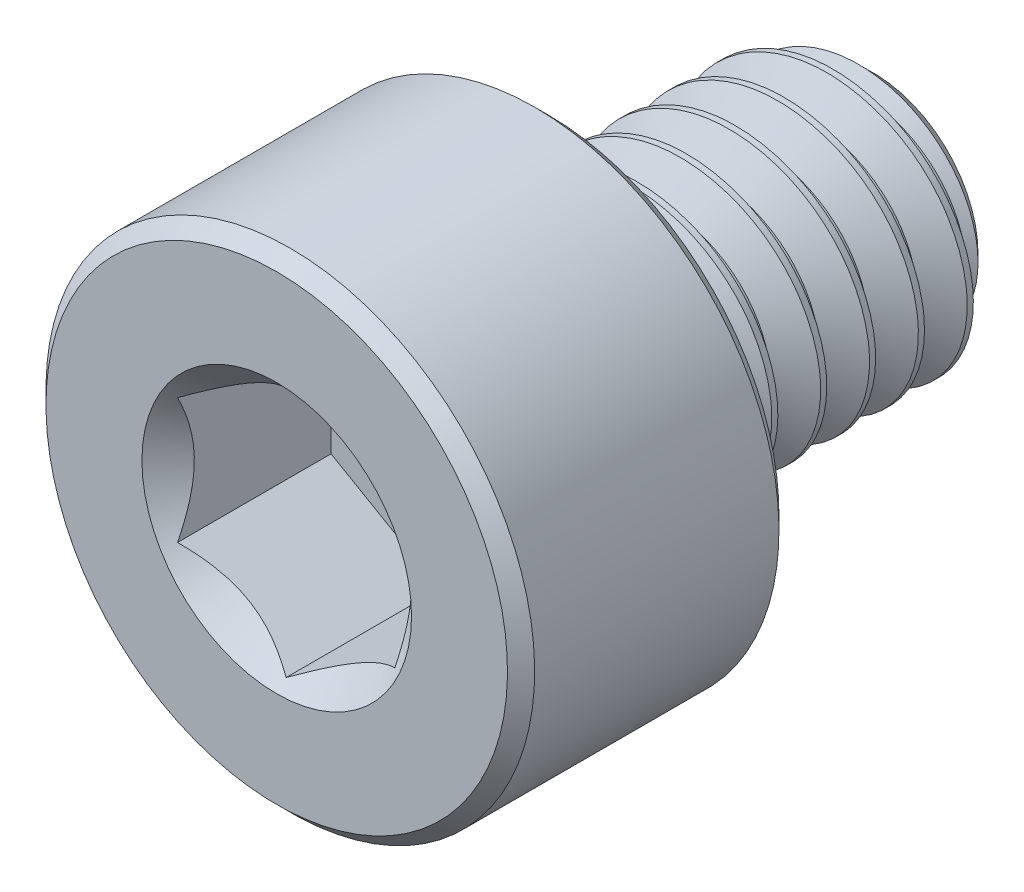
SolidWorks part; units mm, degrees
ref_plane "Front Plane" through (0, 0, 0) normal (0, 0, 1) x (1, 0, 0)
ref_plane "Top Plane" through (0, 0, 0) normal (0, 1, 0) x (1, 0, 0)
ref_plane "Right Plane" through (0, 0, 0) normal (1, 0, 0) x (0, 0, -1)
sketch "Sketch1" plane through (0, 0, 0) normal (1, 0, 0) x (0, 0, -1)
  line L0 (-2.75, 0) -> (2.75, 0) construction
  line L1 (2.75, 0) -> (2.75, 0.9577) construction
  line L2 (2.75, 0.9577) -> (2.4577, 1.25) construction
  line L3 (2.4577, 1.25) -> (2.4125, 1.25) construction
  line L4 (2.4125, 1.25) -> (-0.25, 1.25) construction
  line L5 (-0.25, 1.25) -> (-0.25, 2.25) construction
  line L6 (-0.25, 2.25) -> (-2.75, 2.25) construction
  line L7 (-2.75, 2.25) -> (-2.75, 0) construction
  line L8 (2.75, 0.9577) -> (2.75, 1.25) construction
  line L9 (2.7219, 1.2987) -> (2.9469, 0.909) construction
  line L10 (2.9469, 0.909) -> (3.1719, 1.2987) construction
  line L11 (3.1719, 1.2987) -> (2.7219, 1.2987) construction
  line L12 (2.9469, 1.2987) -> (2.9469, 1.25) construction
  line L13 (2.9469, 0.909) -> (2.9469, 0.9577) construction
  line L14 (2.9187, 0.9577) -> (2.975, 0.9577) construction
  line L15 (2.75, 1.25) -> (3.1437, 1.25) construction
  line L16 (2.7359, 1.2744) -> (3.1578, 1.2744) construction
  line L17 (2.75, 0) -> (2.75, -1.25) construction
  line L18 (-0.375, 2.25) -> (-0.25, 2.125) construction
  line L19 (-2.625, 2.25) -> (-2.75, 2.125) construction
  line L20 (-0.25, 1.25) -> (-0.25, 0) construction
  line L21 (-0.25, 0.625) -> (0.75, 0.625) construction
  line L22 (0.75, 0.625) -> (1.75, 0.625) construction
  line L23 (1.75, 0.625) -> (2.75, 0.625) construction
  line L24 (0.75, 0.625) -> (0.75, 1.25) construction
  line L25 (0.75, 1.25) -> (0.75, 2.25) construction
  line L26 (1.75, 0.625) -> (1.75, 2.25) construction
  point P0 (-2.75, 1)
  point P3 (1.625, 1.25)
  point P4 (0, 0)
  point P18 (1.75, 1.25)
  point P22 (2.9469, 0.9577)
  point P24 (2.4125, 1.25)
  point P25 (2.9469, 1.25)
  point P28 (2.9469, 1.2744)
  point P29 (1.625, -1.25)
  point P30 (0.75, 1.25)
  point P31 (-1.5, 2.25)
  point P37 (-0.6875, 2.25)
  point P38 (-2.5625, 2.25)
  point P45 (0.75, 0.625)
  point P46 (1.75, 0.625)
  dimension "D2" = 0.0563
  dimension "D7" = 0.125
  dimension "D8" = 0.125
  dimension "D9" = 0.125
  dimension "D10" = 0.0625
  dimension "D11" = 0.3125
  dimension "Drive Size" = 2
  dimension "Head Diameter" = 4.5
  dimension "Head Height" = 2.5
  dimension "Thread Pitch" = 0.45
  dimension "Thread Dia" = 2.5
  dimension "Length" = 3
  dimension "D12" = 0.3375
  dimension "D4" = 1.125
  dimension "D3" = 45
sketch "Sketch2" plane through (0, 0, 0) normal (1, 0, 0) x (0, 0, -1)
  line L0 (-2.75, 0) -> (-2.75, 2.125)
  line L1 (-2.625, 2.25) -> (-0.375, 2.25)
  line L2 (-0.25, 2.125) -> (-0.25, 1.375)
  line L4 (2.4577, 1.25) -> (2.75, 0.9577)
  line L5 (2.75, 0.9577) -> (2.75, 0)
  line L6 (-0.25, 2.25) -> (-2.75, 2.25) construction
  line L7 (2.75, 0) -> (-2.75, 0)
  line L8 (-2.625, 2.25) -> (-2.75, 2.125) construction
  line L10 (-2.625, 2.25) -> (-2.75, 2.125)
  line L14 (-0.375, 2.25) -> (-0.25, 2.125) construction
  line L16 (-0.375, 2.25) -> (-0.25, 2.125)
  line L17 (-0.25, 1.25) -> (-0.25, 2.25) construction
  line L19 (-0.125, 1.25) -> (2.4577, 1.25)
  line L20 (2.4125, 1.25) -> (-0.25, 1.25) construction
  arc A1 (-0.25, 1.375) -> (-0.125, 1.25) centre (-0.125, 1.375) ccw
  dimension "D3" = 0.125
revolve "Revolve1" add sketch "Sketch2" angle 360 about L7
sketch "Sketch3" plane through (0, 0, 2.75) normal (0, 0, 1) x (1, 0, 0)
  line L1 (1, -0.5774) -> (1, 0.5774)
  line L2 (1, 0.5774) -> (0, 1.1547)
  line L3 (0, 1.1547) -> (-1, 0.5774)
  line L4 (-1, 0.5774) -> (-1, -0.5774)
  line L5 (-1, -0.5774) -> (0, -1.1547)
  line L6 (0, -1.1547) -> (1, -0.5774)
  circle A0 centre (0, 0) radius 1 construction
  circle A1 centre (0, 0) radius 2.25 construction
  circle A2 centre (0, 0) radius 2.25 construction
  circle A3 centre (0, 0) radius 1.1547 construction
  point P13 (0, 0)
  dimension "D1" = 2.3094
extrude "Cut-Extrude1" cut sketch "Sketch3" against normal offset from surface (1.5 mm away) 1 up to face at (0, 2.125, 0.25)
sketch "Sketch4" plane through (0, 0, 2.75) normal (0, 0, 1) x (1, 0, 0)
  circle A0 centre (0, 0) radius 1.2413
  dimension "D1" = 2.4826
extrude "Cut-Extrude2" cut sketch "Sketch4" against normal up to vertex (1.25 mm away) draft 45 up to point (0, 2.25, 1.5)
sketch "Sketch11" plane through (0, 0, 0) normal (1, 0, 0) x (0, 0, -1)
  line L0 (-2.75, 0) -> (2.75, 0) construction
  line L1 (-2.75, 0) -> (2.75, 0) construction
  line L2 (0.3125, 0) -> (0.3125, 1.25) construction
  line L3 (2.4125, 1.25) -> (-0.25, 1.25) construction
  line L4 (2.1875, 0) -> (2.1875, 1.25) construction
  line L6 (2.75, 0.9577) -> (2.75, 1.25) construction
  point P2 (0.3125, 0)
  point P3 (2.1875, 0)
  dimension "D1" = 0.5625
  dimension "D2" = 0.5625
sketch "Sketch6" plane through (0, 0, -2.75) normal (0, 0, -1) x (-1, 0, 0)
  circle A0 centre (0, 0) radius 1.25
curve "Helix/Spiral1" pitch 0.45 height 3.45 turns 7.6667
sketch "Sketch10" plane through (0, 0, 0) normal (1, 0, 0) x (0, 0, -1)
  line L0 (-0.125, -2.25) -> (-0.125, 2.25)
  line L5 (-2.75, 0) -> (2.75, 0) construction
  line L6 (-0.125, 1.25) -> (-0.125, -1.25) construction
  point P3 (-0.125, 0)
split "Split1" trim tools "Sketch10" bodies to split 106 resulting bodies 114 115
sketch "Sketch7" plane through (0, 0, 0) normal (1, 0, 0) x (0, 0, -1)
  line L0 (2.7359, 1.2744) -> (3.1578, 1.2744)
  line L1 (3.1578, 1.2744) -> (2.975, 0.9577)
  line L2 (2.975, 0.9577) -> (2.9187, 0.9577)
  line L3 (2.9187, 0.9577) -> (2.7359, 1.2744)
sweep "Cut-Sweep1" cut profiles "Sketch7" path "Helix/Spiral1" align with end faces yes
sketch "Sketch8" plane through (0, 0, 0) normal (1, 0, 0) x (0, 0, -1)
  line L0 (-0.25, 0) -> (-0.25, 1.25)
  line L1 (-0.125, -1.25) -> (-0.125, 1.25) construction
  line L2 (-0.25, 1.25) -> (-0.125, 1.25)
  line L4 (-0.125, 1.25) -> (0.5967, 0)
  line L5 (0.5967, 0) -> (-0.25, 0)
  line L6 (2.4125, 1.25) -> (-0.25, 1.25) construction
  line L7 (-2.75, 0) -> (2.75, 0) construction
  dimension "D1" = 60
revolve "Revolve2" add sketch "Sketch8" angle 360 about L5
equation "\"D2@Sketch1\" = \"Thread Pitch@Sketch1\" / 8"
equation "\"D4@Helix/Spiral1\" = \"Thread Pitch@Sketch1\""
equation "\"D7@Sketch1\" = \"Head Height@Sketch1\" * .05"
equation "\"D8@Sketch1\"=\"D7@Sketch1\""
equation "\"D9@Sketch1\"=\"D7@Sketch1\""
equation "\"D10@Sketch1\"=\"D7@Sketch1\"/2"
equation "\"D11@Sketch1\"=\"D10@Sketch1\"*5"
equation "\"D4@Sketch1\"=\"Thread Pitch@Sketch1\"*2.5"
equation "\"D12@Sketch1\"=\"Thread Pitch@Sketch1\"*.75"
equation "\"D3@Helix/Spiral1\"=\"Length@Sketch1\"+\"Thread Pitch@Sketch1\""
equation "\"D3@Sketch2\"=\"Thread Dia@Sketch1\"*0.05"
equation "\"D1@Sketch11\"=\"Length@Sketch1\"*0.1875"
equation "\"D2@Sketch11\"=\"D1@Sketch11\""
equation "\"D1@Sketch4\"=\"D1@Sketch3\"*1.075"
